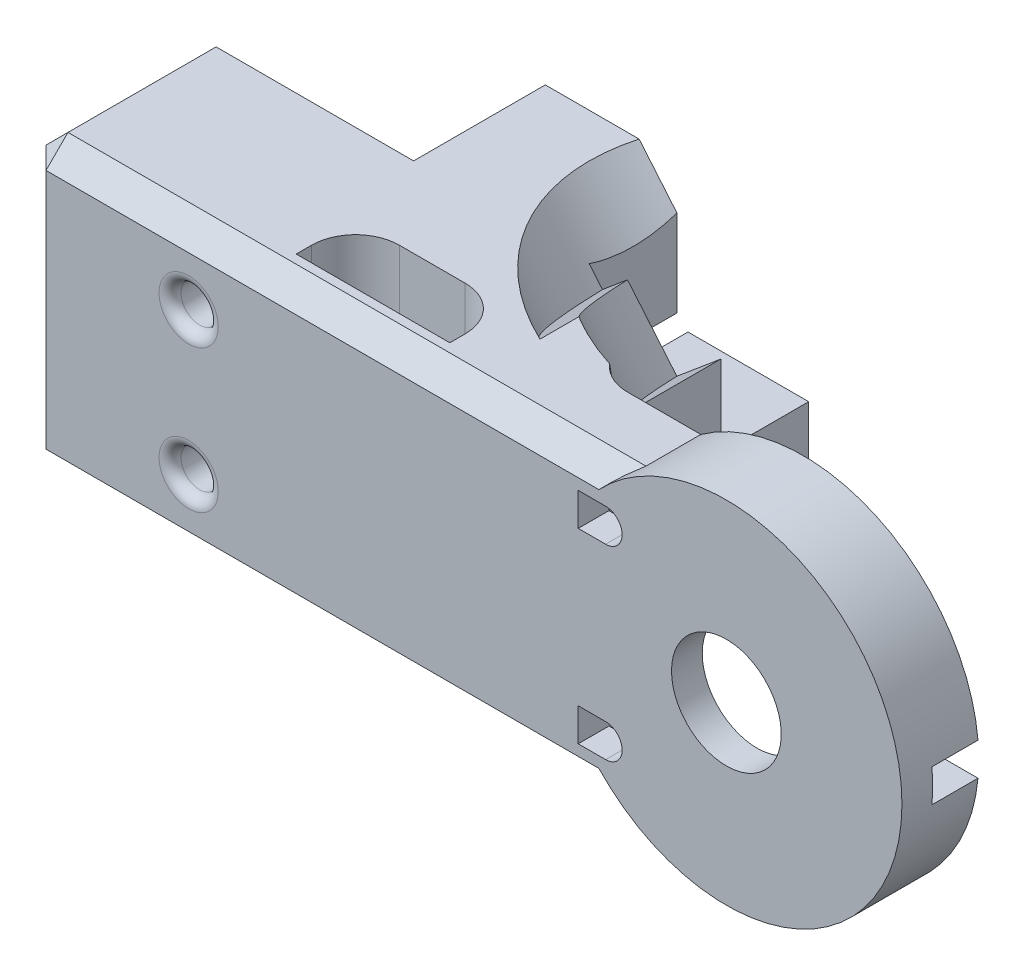
SolidWorks part; units mm, degrees
ref_plane "Front Plane" through (0, 0, 0) normal (0, 0, 1) x (1, 0, 0)
ref_plane "Top Plane" through (0, 0, 0) normal (0, 1, 0) x (1, 0, 0)
ref_plane "Right Plane" through (0, 0, 0) normal (1, 0, 0) x (0, 0, -1)
sketch "Sketch1" plane through (0, 0, 0) normal (0, 0, 1) x (1, 0, 0)
  line L0 (-1000, 0) -> (49000, 0) construction
  line L1 (-1003.2111, 6.5) -> (48996.7889, 6.5) construction
  line L2 (-1004.8419, -6.5) -> (48995.1581, -6.5) construction
  line L3 (-15, -6.5) -> (-15, 6.5)
  line L4 (-15, 6.5) -> (-4.6637, 6.5)
  line L5 (-15, -6.5) -> (-4.6637, -6.5)
  arc A0 (-4.6637, -6.5) -> (-4.6637, 6.5) centre (0, 0) ccw
  arc A1 (-8, 0) -> (-4.6637, -6.5) centre (0, 0) ccw construction
  arc A2 (-4.6637, 6.5) -> (-8, 0) centre (0, 0) ccw construction
  point P12 (-15, 0)
  dimension "D1" = 16
  dimension "D2" = 13
  dimension "D3" = 15
extrude "Boss-Extrude1" add sketch "Sketch1" along normal blind 3.5
sketch "Sketch2" plane through (0, 0, 0) normal (0, 0, -1) x (-1, 0, 0)
  line L0 (-1000, 0) -> (49000, 0) construction
  line L1 (0, -1000) -> (0, 49000) construction
  line L3 (-5.75, -1008.4841) -> (-5.75, -0.75) construction
  line L4 (-998.5902, -5.75) -> (49001.4098, -5.75) construction
  line L5 (-997.2865, 5.75) -> (49002.7135, 5.75) construction
  line L6 (-5.75, -0.75) -> (-7.9648, -0.75)
  line L7 (-5.75, 0.75) -> (-7.9648, 0.75)
  line L8 (-5.75, -2.5) -> (-5.75, -0.75)
  line L9 (-5.75, -2.5) -> (-2.5, -5.75)
  line L10 (-5.75, 2.5) -> (-2.5, 5.75)
  line L11 (-2.5, -5.75) -> (6.75, -5.75)
  line L12 (-2.5, 5.75) -> (6.75, 5.75)
  line L13 (6.75, -1004.2518) -> (6.75, 48995.7482) construction
  line L15 (6.75, -5.75) -> (6.75, 5.75)
  line L16 (-5.75, 0) -> (-5.75, 0.75) construction
  line L17 (-5.75, 0.75) -> (-5.75, 2.5)
  line L18 (-5.75, 0) -> (-5.75, 0.75) construction
  line L19 (-5.75, 0.75) -> (-5.75, 48991.5159) construction
  line L20 (-5.75, -0.75) -> (-5.75, 0) construction
  line L21 (-5.75, -0.75) -> (-5.75, 0) construction
  line L22 (-2.5, -1002.5522) -> (-2.5, 48997.4478) construction
  arc A0 (-7.9648, -0.75) -> (-7.9648, 0.75) centre (0, 0) cw
  circle A1 centre (0, 0) radius 8 construction
  point P25 (-5.5, 0)
  dimension "D6" = 8
  dimension "D1" = 5.75
  dimension "D2" = 5.75
  dimension "D3" = 5.75
  dimension "D4" = 0.75
  dimension "D5" = 0.75
  dimension "D7" = 5
  dimension "D8" = 45
  dimension "D9" = 45
  dimension "D10" = 2.5
  dimension "D11" = 6.75
extrude "Cut-Extrude1" cut sketch "Sketch2" against normal blind 2.1
sketch "Sketch3" plane through (0, 0, 2.1) normal (0, 0, -1) x (-1, 0, 0)
  line L0 (5.5, -5) -> (6.75, -5)
  line L1 (5.5, -3.5) -> (6.75, -3.5)
  line L2 (5.5, 3.5) -> (6.75, 3.5)
  line L3 (5.5, 5) -> (6.75, 5)
  line L5 (6.75, -5.75) -> (6.75, 5.75) construction
  line L7 (6.75, 5) -> (6.75, 3.5)
  line L9 (6.75, -3.5) -> (6.75, -5)
  circle A0 centre (0, 0) radius 2.5
  arc A1 (5.5, -3.5) -> (5.5, -5) centre (5.5, -4.25) ccw
  arc A2 (5.5, 5) -> (5.5, 3.5) centre (5.5, 4.25) ccw
  arc A6 (5.5, -5) -> (5.5, -3.5) centre (5.5, -4.25) ccw construction
  arc A7 (5.5, 3.5) -> (5.5, 5) centre (5.5, 4.25) ccw construction
  dimension "D1" = 5
  dimension "D2" = 1.5
  dimension "D3" = 1.5
extrude "Cut-Extrude2" cut sketch "Sketch3" against normal through all
sketch "Sketch5" plane through (0, 0, 3.5) normal (0, 0, -1) x (-1, 0, 0)
  line L1 (15, -6.5) -> (10, -6.5)
  line L2 (15, -6.5) -> (15, 6.5)
  line L3 (15, 6.5) -> (10, 6.5)
  line L4 (10, -6.5) -> (10, 6.5)
  line L5 (15, -6.5) -> (4.6637, -6.5) construction
  line L6 (4.6637, 6.5) -> (15, 6.5) construction
  line L7 (15, 6.5) -> (15, -6.5) construction
  dimension "D1" = 10
extrude "Boss-Extrude3" add sketch "Sketch5" along normal blind 11.75
ref_plane "Plane1" through (-32, 0, 0) normal (1, 0, 0) x (0, 0, -1)
sketch "Sketch6" plane through (-15, 0, 0) normal (-1, 0, 0) x (0, 0, 1)
  line L1 (-8.25, 6.5) -> (3.5, 6.5)
  line L2 (-8.25, 6.5) -> (-8.25, -6.5)
  line L3 (-8.25, -6.5) -> (3.5, -6.5)
  line L4 (3.5, 6.5) -> (3.5, -6.5)
extrude "Boss-Extrude4" add sketch "Sketch6" along normal up to surface (17 mm away) up to plane "Plane1"
sketch "Sketch7" plane through (0, 0, -8.25) normal (0, 0, -1) x (-1, 0, 0)
  line L0 (10, -6.5) -> (32, -6.5) construction
  line L1 (32, 6.5) -> (22, 6.5)
  line L2 (32, 6.5) -> (32, -6.5)
  line L3 (32, -6.5) -> (22, -6.5)
  line L4 (22, 6.5) -> (22, -6.5)
  dimension "D1" = 10
extrude "Cut-Extrude3" cut sketch "Sketch7" against normal blind 4
chamfer "Chamfer1" distance 1 angle 45 5 edges at (-32, -6.5, -0.375) (-32, 0, 3.5) (-32, 6.5, -0.375) (-18.3318, -6.5, 3.5) (-18.3318, 6.5, 3.5)
sketch "Sketch8" plane through (0, 0, -4.25) normal (0, 0, -1) x (-1, 0, 0)
  line L0 (24.5, -994.4359) -> (24.5, 49005.5641) construction
  line L1 (-965.4443, 3.25) -> (49034.5557, 3.25) construction
  line L2 (-964.8524, -3.25) -> (49035.1476, -3.25) construction
  line L3 (31, 6.5) -> (22, 6.5) construction
  line L4 (22, 6.5) -> (22, -6.5) construction
  line L5 (22, -6.5) -> (31, -6.5) construction
  circle A0 centre (24.5, 3.25) radius 0.85
  circle A1 centre (24.5, -3.25) radius 0.85
  dimension "D4" = 1.7
  dimension "D5" = 1.7
  dimension "D1" = 3.25
  dimension "D2" = 2.5
  dimension "D3" = 3.25
extrude "Cut-Extrude4" cut sketch "Sketch8" against normal through all
fillet "Fillet1" radius 0.5 2 edges at (-25.35, -3.25, 3.5) (-25.35, 3.25, 3.5)
sketch "Sketch17" plane through (0, 0, -8.25) normal (0, 0, -1) x (-1, 0, 0)
  line L0 (22, 6.5) -> (16, 6.5)
  line L3 (22, 6.5) -> (10, 6.5) construction
  line L6 (16, 6.5) -> (16, 0.5)
  line L23 (10, -6.5) -> (22, -6.5) construction
  line L24 (16, -6.5) -> (10, -6.5)
  line L25 (10, -6.5) -> (10, 0)
  line L26 (10, 6.5) -> (10, -6.5) construction
  line L27 (10, 0) -> (15.5, 0)
  line L28 (22, 6.5) -> (22, -6.5) construction
  line L29 (22, 0) -> (22, 6.5)
  line L30 (16, 0.5) -> (16.5, 0)
  line L31 (15.5, 0) -> (16, -0.5)
  line L32 (16, 0) -> (16, -0.5) construction
  line L33 (16, -0.5) -> (16, -6.5)
  line L34 (16, 0) -> (16.5, 0) construction
  line L35 (16.5, 0) -> (22, 0)
  line L36 (16, 0.5) -> (16, 0) construction
  line L37 (15.5, 0) -> (16, 0) construction
  circle A2 centre (16, 0) radius 0.5 construction
  dimension "D1" = 1
sketch "Sketch19" plane through (-6.75, 0, 0) normal (1, 0, 0) x (0, 0, -1)
  line L1 (-2.1, 4.5) -> (0.6, 4.5)
  line L2 (-2.1, 4.5) -> (-2.1, -4.5)
  line L3 (-2.1, -4.5) -> (0.6, -4.5)
  line L4 (0.6, 4.5) -> (0.6, -4.5)
  line L9 (-2.1, -3.5) -> (-2.1, 3.5) construction
  point P4 (0.6, 0)
  dimension "D1" = 2.7
  dimension "D2" = 9
extrude "Cut-Extrude10" cut sketch "Sketch19" against normal blind 14.25
sketch "Sketch20" plane through (0, 4.5, 0) normal (0, -1, 0) x (1, 0, 0)
  line L0 (-21, -0.6) -> (-10, -0.6) construction
  line L1 (-21, 2.1) -> (-14, 2.1)
  line L2 (-21, 2.1) -> (-21, -0.6)
  line L3 (-21, -0.6) -> (-14, -0.6)
  line L4 (-14, 2.1) -> (-14, -0.6)
  dimension "D1" = 7
extrude "Cut-Extrude11" cut sketch "Sketch20" against normal through all
fillet "Fillet4" radius 3 2 edges at (-12, 4.5, -0.6) (-15.5, -4.5, -0.6)
sketch "Sketch23" plane through (0, 0, 0) normal (0, 0, -1) x (-1, 0, 0)
  line L0 (6.75, 4.5) -> (10, 4.5)
  line L1 (6.75, 3.315) -> (6.75, 5.75) construction
  line L2 (10, 6.5) -> (10, 3.315) construction
  line L3 (10, 4.5) -> (10, -4.5)
  line L4 (10, -4.5) -> (6.75, -4.5)
  line L5 (6.75, -5.75) -> (6.75, -3.315) construction
  line L6 (6.75, -4.5) -> (6.75, 4.5)
  line L7 (14, 4.5) -> (6.75, 4.5) construction
  line L8 (21, -4.5) -> (6.75, -4.5) construction
extrude "Cut-Extrude14" cut sketch "Sketch23" against normal up to surface (2.1 mm away) and the other way through all up to face at (-2.5, 0, 2.1)
fillet "Fillet5" radius 2 8 edges at (-21, -3.5275, 0.1751) (-14, 4.0075, -0.6) (-21, 2.4925, -0.6) (-10, -5.5, 0) (-10, 5.5, 0) (-10, -4.5, 1.05) (-10, 4.5, 1.05) (-14, 3.5275, 0.1751)
extrude "Boss-Extrude7" add sketch "Sketch17" along normal blind 2
sketch "Sketch21" plane through (0, 0, -8.25) normal (0, 0, -1) x (-1, 0, 0)
  line L0 (10, 6.5) -> (10, 0)
  line L1 (10, 0) -> (15.5, 0)
  line L2 (15.5, 0) -> (16, -0.5)
  line L3 (16, -0.5) -> (16, -6.5)
  line L4 (16, -6.5) -> (22, -6.5)
  line L5 (22, -6.5) -> (22, 0)
  line L6 (22, 0) -> (16.5, 0)
  line L7 (16.5, 0) -> (16, 0.5)
  line L8 (16, 0.5) -> (16, 6.5)
  line L9 (16, 6.5) -> (10, 6.5)
extrude "Cut-Extrude12" cut sketch "Sketch21" against normal blind 2
sketch "Sketch22" plane through (-32, 0, 0) normal (-1, 0, 0) x (0, 0, 1)
  line L0 (-2.125, -5.5) -> (-2.125, 5.5) construction
  line L1 (-4.25, -5.5) -> (2.5, -5.5) construction
  line L2 (2.5, 5.5) -> (-4.25, 5.5) construction
  line L3 (-4.25, -5.5) -> (-4.25, 5.5) construction
  arc A0 (-2.125, -1.625) -> (-2.125, -0.475) centre (-2.125, -1.05) ccw
  arc A1 (-2.125, 0.475) -> (-2.125, 1.625) centre (-2.125, 1.05) ccw
  arc A2 (-2.125, -0.475) -> (-2.125, -1.625) centre (-2.125, -1.05) ccw construction
  arc A3 (-2.125, 1.625) -> (-2.125, 0.475) centre (-2.125, 1.05) ccw construction
  ellipse E0 centre (-2.125, -1.05) end of major axis (-2.875, -1.05) minor radius 0.575 (-2.125, -0.475) -> (-2.125, -1.625) ccw
  ellipse E1 centre (-2.125, 1.05) end of major axis (-1.375, 1.05) minor radius 0.575 (-2.125, 1.625) -> (-2.125, 0.475) ccw
  ellipse E2 centre (-2.125, -1.05) end of major axis (-2.875, -1.05) minor radius 0.575 (-2.125, -1.625) -> (-2.125, -0.475) ccw construction
  ellipse E3 centre (-2.125, 1.05) end of major axis (-1.375, 1.05) minor radius 0.575 (-2.125, 0.475) -> (-2.125, 1.625) ccw construction
  point P10 (-2.125, 0)
  dimension "D2" = 1.15
  dimension "D3" = 1.15
  dimension "D1" = 1.05
  dimension "D4" = 2.1
  dimension "D5" = 2.125
  dimension "D6" = 0.75
  dimension "D7" = 0.75
extrude "Cut-Extrude13" cut sketch "Sketch22" against normal through all
fillet "Fillet6" radius 0.25 8 edges at (-32, 1.05, -1.55) (-32, -1.05, -1.55) (-10, 1.05, -1.55) (-10, -1.05, -1.55) (-10, 1.05, -2.875) (-32, 1.05, -2.875) (-10, -1.05, -2.875) (-32, -1.05, -2.875)
ref_plane "Plane2" through (0, 0, -8.25) normal (0, 0, 1) x (1, 0, 0)
sketch "Sketch25" plane through (0, 0, -8.25) normal (0, 0, 1) x (1, 0, 0)
  line L0 (-18, 6.5) -> (-6.6432, 6.5)
  line L1 (-16, 1.515) -> (-16, 6.5) construction
  line L2 (-5.8095, 5.5) -> (-31, 5.5) construction
  line L3 (-15.5574, 3.589) -> (-18, 6.5)
  line L4 (-31, 6.5) -> (-4.6637, 6.5) construction
  line L6 (-32, -5.5) -> (-32, 5.5) construction
  line L7 (-15.5574, 3.589) -> (-14.4466, 4.5211)
  line L8 (-14.4466, 4.5211) -> (-12.1969, 1.8399)
  line L9 (-12.1969, 1.8399) -> (-6.6432, 6.5)
  line L15 (-16.3038, 5.5) -> (-10, 5.5) construction
  line L20 (0, 0) -> (-9.2453, 11.0181) construction
  dimension "D1" = 40
  dimension "D2" = 3.8
  dimension "D3" = 2
  dimension "D4" = 1.45
  dimension "D5" = 3.5
ref_axis "Axis1" through (0, 0, -8.25) along (-0.6428, 0.766, 0)
revolve "Cut-Revolve1" cut sketch "Sketch25" angle 360 about L20
